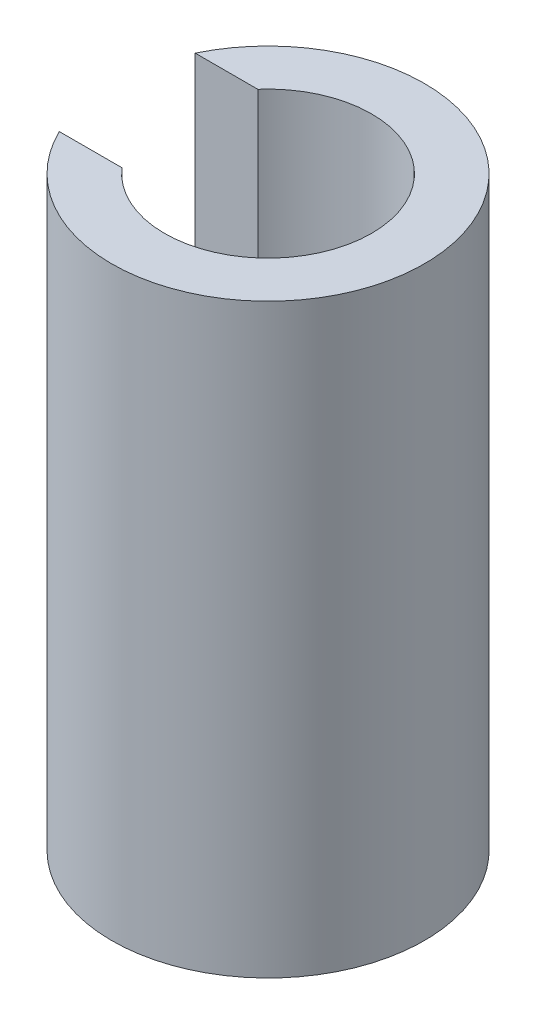
SolidWorks part; units mm, degrees
ref_plane "前基準面" through (0, 0, 0) normal (0, 0, 1) x (1, 0, 0)
ref_plane "上基準面" through (0, 0, 0) normal (0, 1, 0) x (1, 0, 0)
ref_plane "右基準面" through (0, 0, 0) normal (1, 0, 0) x (0, 0, -1)
ref_axis "基準軸1" through (0, -55, 0) along (0, 1, 0)
ref_axis "基準軸2" through (-88.99, 0, 0) along (1, 0, 0)
ref_axis "基準軸3" through (0, 0, 55) along (0, 0, -1)
sketch "草圖1" plane through (0, 0, 0) normal (0, 1, 0) x (1, 0, 0)
  circle A0 centre (0, 0) radius 2.65
  circle A1 centre (0, 0) radius 4
  dimension "D1" = 5.3
  dimension "D2" = 8
extrude "填料-伸長1" add sketch "草圖1" along normal blind 15
sketch "草圖2" plane through (0, 15, 0) normal (0, 1, 0) x (1, 0, 0)
  line L1 (-4, -1.7385) -> (-2, -1.7385)
  line L2 (-4, -1.7385) -> (-4, 1.7385)
  line L3 (-4, 1.7385) -> (-2, 1.7385)
  line L4 (-2, -1.7385) -> (-2, 1.7385)
  line L5 (-55, 0) -> (55, 0) construction
  circle A0 centre (0, 0) radius 4 construction
  circle A1 centre (0, 0) radius 2.65 construction
  point P4 (-2, 0)
  dimension "D1" = 2
extrude "除料-伸長1" cut sketch "草圖2" against normal blind 15
